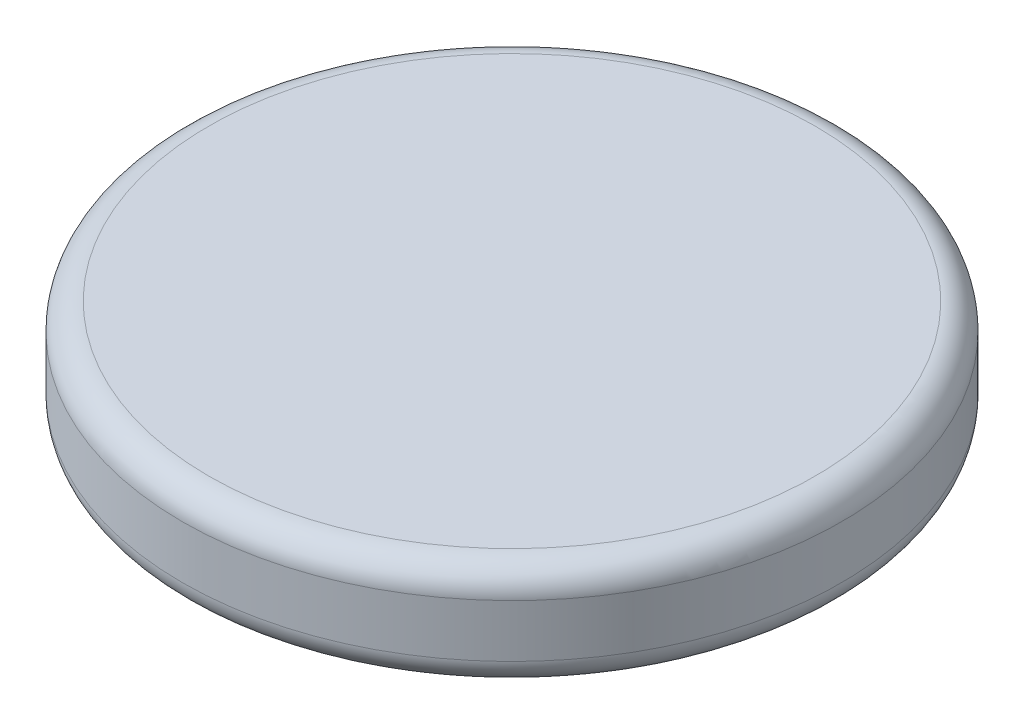
SolidWorks part; units mm, degrees
ref_plane "Спереди" through (0, 0, 0) normal (0, 0, 1) x (1, 0, 0)
ref_plane "Сверху" through (0, 0, 0) normal (0, 1, 0) x (1, 0, 0)
ref_plane "Справа" through (0, 0, 0) normal (1, 0, 0) x (0, 0, -1)
other "Configuration Table"
sketch "Эскиз1" plane through (0, 0, 0) normal (0, 1, 0) x (1, 0, 0)
  line L1 (3.1, -3.1) -> (-3.1, -3.1)
  line L2 (3.1, -3.1) -> (3.1, 3.1)
  line L3 (3.1, 3.1) -> (-3.1, 3.1)
  line L4 (-3.1, -3.1) -> (-3.1, 3.1)
  line L5 (3.1, -3.1) -> (-3.1, 3.1) construction
  line L6 (3.1, 3.1) -> (-3.1, -3.1) construction
  line L7 (1.9, -1.9) -> (-1.9, -1.9)
  line L8 (1.9, -1.9) -> (1.9, 1.9)
  line L9 (1.9, 1.9) -> (-1.9, 1.9)
  line L10 (-1.9, -1.9) -> (-1.9, 1.9)
  line L11 (1.9, -1.9) -> (-1.9, 1.9) construction
  line L12 (1.9, 1.9) -> (-1.9, -1.9) construction
  circle A0 centre (0, 0) radius 12.5
  circle A1 centre (0, 0) radius 11.3
  point P13 (1.9, 0)
  dimension "D4" = 25
  dimension "D5" = 1.2
  dimension "D1" = 3.8
  dimension "D2" = 1.2
extrude "Бобышка-Вытянуть1" add sketch "Эскиз1" against normal blind 1.2 contours A1 L1 L4 L3 L2 | A0 A1 | L10 L7 L8 L9 | L4 L1 L2 L3 L7 L10 L9 L8 region at (0, 0, 3.0123) region at (0, 0, 0) region at (-12.1464, 0, 0) region at (-10.9804, 0, 0)
extrude "Бобышка-Вытянуть2" add sketch "Эскиз1<3>" against normal blind 4 contours A0 A1 region at (-12.1464, 0, 0)
sketch "Эскиз1<3>" plane through (0, 0, 0) normal (0, 1, 0) x (1, 0, 0) same geometry as "Эскиз1"
extrude "Бобышка-Вытянуть3" add sketch "Эскиз1<5>" against normal blind 2 contours L4 L1 L2 L3 L7 L10 L9 L8 | L10 L7 L8 L9 region at (0, 0, 3.0123) region at (0, 0, 0)
sketch "Эскиз1<5>" plane through (0, 0, 0) normal (0, 1, 0) x (1, 0, 0) same geometry as "Эскиз1"
extrude "Бобышка-Вытянуть4" add sketch "Эскиз1<6>" against normal blind 3 from surface contours L4 L1 L2 L3 L7 L10 L9 L8 region at (0, 0, 3.0123) starting at face at (0, -2, 0)
sketch "Эскиз1<6>" plane through (0, 0, 0) normal (0, 1, 0) x (1, 0, 0) same geometry as "Эскиз1"
fillet "Скругление1" radius 1 2 edges at (0, -4, 12.5) (0, 0, 12.5)
sketch "Эскиз2" plane through (0, -5, 0) normal (0, -1, 0) x (1, 0, 0)
  line L1 (1.9, -1.9) -> (-1.9, -1.9)
  line L2 (1.9, -1.9) -> (1.9, 1.9)
  line L3 (1.9, 1.9) -> (-1.9, 1.9)
  line L4 (-1.9, -1.9) -> (-1.9, 1.9)
  line L5 (1.9, -1.9) -> (-1.9, 1.9) construction
  line L6 (1.9, 1.9) -> (-1.9, -1.9) construction
  line L7 (1.7, -1.7) -> (-1.7, -1.7)
  line L8 (1.7, -1.7) -> (1.7, 1.7)
  line L9 (1.7, 1.7) -> (-1.7, 1.7)
  line L10 (-1.7, -1.7) -> (-1.7, 1.7)
  line L11 (1.7, -1.7) -> (-1.7, 1.7) construction
  line L12 (1.7, 1.7) -> (-1.7, -1.7) construction
  point P0 (0, 0)
  point P7 (0, 0)
  dimension "D1" = 0.2
extrude "Бобышка-Вытянуть5" add sketch "Эскиз2" against normal blind 0.8
